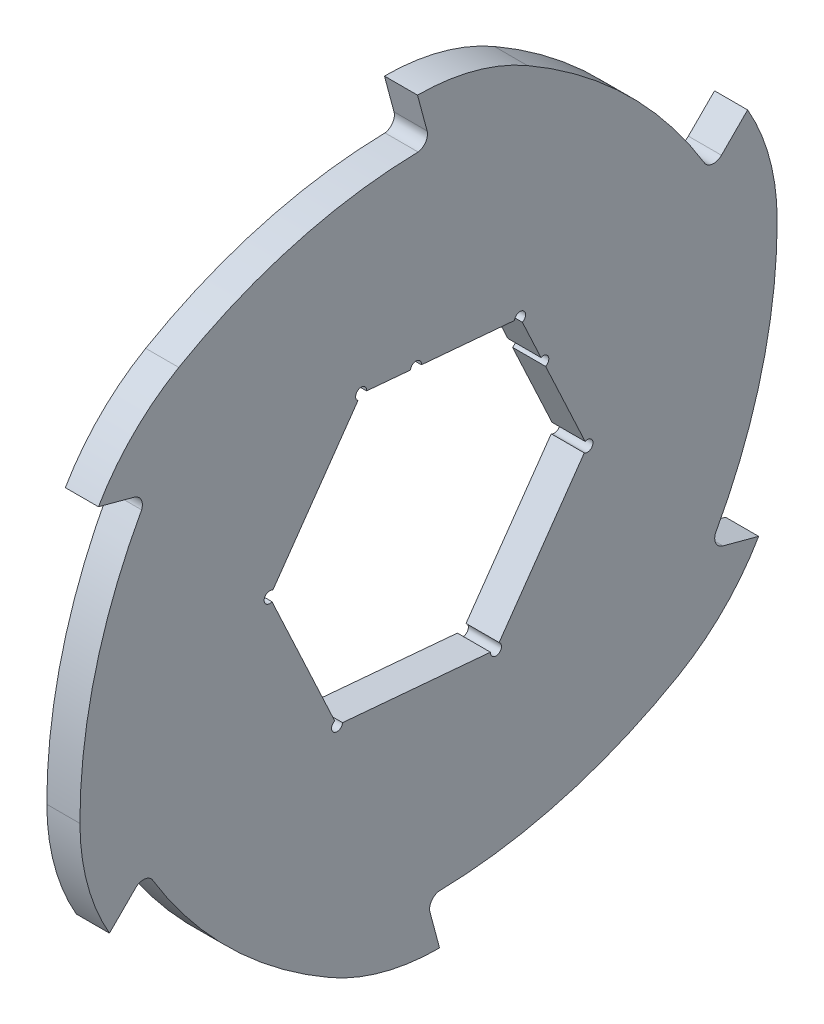
SolidWorks part; units mm, degrees
note: '?' marks a value the reader was unsure of.
material "1.0037 (S235JR)"
ref_plane "Alzado" through (0, 0, 0) normal (0, 0, 1) x (1, 0, 0)
ref_plane "Planta" through (0, 0, 0) normal (0, 1, 0) x (1, 0, 0)
ref_plane "Vista lateral" through (0, 0, 0) normal (1, 0, 0) x (0, 0, -1)
sketch "Sketch1" plane through (0, 0, 0) normal (1, 0, 0) x (0, 0, -1)
  line L0 (-56.6126, 0) -> (65.57, 0) construction
  line L1 (16.5908, 23.6942) -> (-12.2243, 26.2152)
  line L2 (-12.2243, 26.2152) -> (-28.8152, 2.521)
  line L3 (-28.8152, 2.521) -> (-16.5908, -23.6942)
  line L4 (-16.5908, -23.6942) -> (12.2243, -26.2152)
  line L5 (12.2243, -26.2152) -> (28.8152, -2.521)
  line L6 (28.8152, -2.521) -> (16.5908, 23.6942)
  circle A0 centre (0, 0) radius 25.05 construction
  circle A1 centre (0, 0) radius 59
  dimension "D2" = 118
  dimension "D1" = 50.1
  dimension "D3" = 5
extrude "Extrude1" add sketch "Sketch1" along normal mid plane 6
ref_axis "Axis1" through (-5.5, 0, 0) along (1, 0, 0)?
sketch "Sketch2" plane through (0, 0, 0) normal (1, 0, 0) x (0, 0, -1)
  line L0 (-2, 67.9618) -> (-0.2627, 61.4781)
  line L1 (0, 0) -> (0, 77.6328) construction
  line L4 (-2.1226, 58.9618) -> (0, 0) construction
  circle A0 centre (0, 0) radius 59 construction
  arc A1 (-2, 67.9618) -> (17.9271, 62.6448) centre (-2, 27.9618) cw
  arc A3 (51.2137, 29.2943) -> (-2.1226, 58.9618) centre (0, 0) ccw
  arc A4 (-0.2627, 61.4781) -> (-2.1226, 58.9618) centre (-2.1946, 60.9605) cw
  arc A5 (17.9271, 62.6448) -> (51.2137, 29.2943) centre (-26.9089, -15.3919) cw
  point P10 (-2, 67.9618)
  dimension "D2" = 40
  dimension "D4" = 2
  dimension "D3" = 9
  dimension "D6" = 90
  dimension "D1" = 15
  dimension "D5" = 2
extrude "Extrude2" add sketch "Sketch2" against normal mid plane 6
fillet "Fillet1" [suppressed] radius 0.6
pattern_circular "CirPattern1" count 6 over 360 about axis through (0, 0, 0) along (1, 0, 0) of "Extrude2", "Fillet1"
sketch "Sketch4" [suppressed] plane through (3, 0, 0) normal (1, 0, 0) x (0, 0, -1)
  circle A0 centre (0, 0) radius 67.9646 construction
  dimension "D1" = 135.9291
hole_wizard "Ø2.0 (2) Diameter Hole1" positions "Sketch5" profile "Sketch7" hole size "Ø2.0" standard "ISO" end condition up to next
sketch "Sketch5" plane through (3, 0, 0) normal (1, 0, 0) x (0, 0, -1)
  point P0 (-12.2243, 26.2152)
  point P7 (16.5908, 23.6942)
  point P8 (28.8152, -2.521)
  point P9 (12.2243, -26.2152)
  point P10 (-16.5908, -23.6942)
  point P11 (-28.8152, 2.521)
  dimension "D1" = 6
sketch "Sketch7" plane through (3, 26.2152, 12.2243) normal (0, 1, 0) x (0, 0, -1)
  line L0 (0, 0) -> (0, 6)
  line L1 (0, 6) -> (1, 6)
  line L2 (1, 6) -> (1, 0)
  line L5 (1, 0) -> (0, 0)
  line L11 (0, -6.35) -> (0, 107.95) construction
  dimension "Diámetro de taladro hasta el siguiente" = 2
  dimension "Profundidad de taladro hasta el siguiente" = 6
hole_wizard "Ø2.0 (2) Diameter Hole3" positions "Sketch10" profile "Sketch11" hole size "Ø2.0" standard "ISO" end condition up to next
sketch "Sketch10" plane through (3, 0, 0) normal (1, 0, 0) x (0, 0, -1)
  line L0 (-11.2281, 26.128) -> (-2.2872, 25.3458) construction
  line L1 (15.5946, 23.7813) -> (-11.2281, 26.128) construction
  line L2 (-2.2872, 25.3458) -> (6.6537, 24.5636) construction
  line L3 (6.6537, 24.5636) -> (15.5946, 23.7813) construction
  point P2 (-2.2872, 25.3458)
sketch "Sketch11" plane through (3, 25.3458, 2.2872) normal (0, 1, 0) x (0, 0, -1)
  line L0 (0, 0) -> (0, 6.001)
  line L1 (0, 6.001) -> (1, 6.001)
  line L2 (1, 6.001) -> (1, 0)
  line L5 (1, 0) -> (0, 0)
  line L11 (0, -6.35) -> (0, 107.95) construction
  dimension "Diámetro de taladro hasta el siguiente" = 2
  dimension "Profundidad de taladro hasta el siguiente" = 6.001
hole_wizard "Ø2.0 (2) Diameter Hole4" [suppressed] positions "Sketch12" profile "Sketch13" hole size "Ø2.0" standard "ISO"
sketch "Sketch12" plane through (3, 0, 0) normal (1, 0, 0) x (0, 0, -1)
  line L0 (13.4626, 25.05) -> (-3.4875, 25.05) construction
  point P0 (4.9875, 25.05)
sketch "Sketch13" plane through (3, 25.05, -4.9875) normal (0, 1, 0) x (0, 0, -1)
  line L0 (0, 0) -> (0, 6)
  line L1 (0, 6) -> (1, 6)
  line L2 (1, 6) -> (1, 0)
  line L5 (1, 0) -> (0, 0)
  line L11 (0, -6.35) -> (0, 107.95) construction
  dimension "Diámetro de taladro hasta el siguiente" = 2
  dimension "Profundidad de taladro hasta el siguiente" = 6
pattern_circular "CirPattern2" count 2 every 60 about axis through (-5.5, 0, 0) along (1, 0, 0) of "Ø2.0 (2) Diameter Hole3" reverse direction yes
pattern_circular "CirPattern3" [suppressed] count 1 every? 60? about axis through (-5.5, 0, 0) along (1, 0, 0)
equation "\"D1@Extrude2\"=\"D1@Extrude1\""
